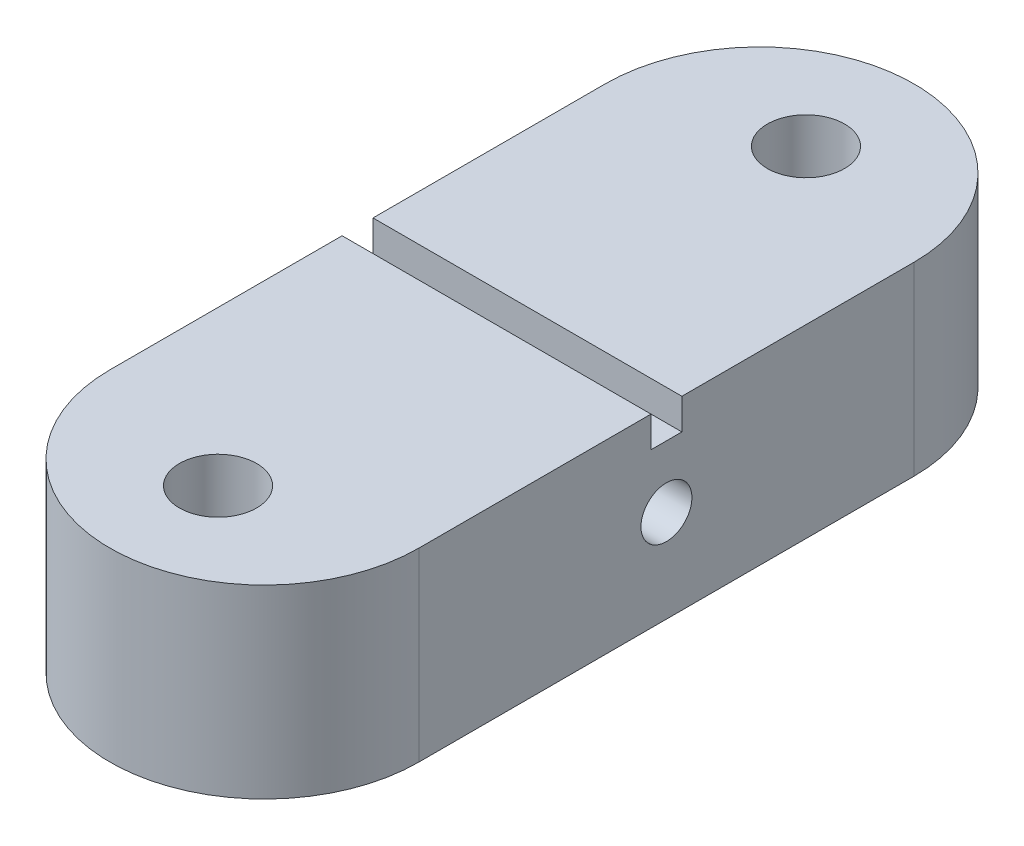
SolidWorks part; units mm, degrees
material "ASTM A36 Steel"
ref_plane "Front Plane" through (0, 0, 0) normal (0, 0, 1) x (1, 0, 0)
ref_plane "Top Plane" through (0, 0, 0) normal (0, 1, 0) x (1, 0, 0)
ref_plane "Right Plane" through (0, 0, 0) normal (1, 0, 0) x (0, 0, -1)
sketch "Sketch1" plane through (0, 0, 0) normal (0, 0, 1) x (1, 0, 0)
  line L1 (10, 6) -> (-10, 6)
  line L2 (10, 6) -> (10, -6)
  line L3 (10, -6) -> (-10, -6)
  line L4 (-10, 6) -> (-10, -6)
  line L5 (0, -6) -> (0, 6) construction
  line L6 (10, 0) -> (-10, 0) construction
  point P0 (0, 0)
  dimension "D1" = 20
  dimension "D2" = 12
extrude "Boss-Extrude1" add sketch "Sketch1" along normal mid plane 52.07
hole_wizard "M6x1.0 Tapped Hole1" positions "Sketch2" profile "Sketch3" tap size "M6x1.0" standard "ANSI Metric" end condition through all
sketch "Sketch2" plane through (0, 6, 0) normal (0, 1, 0) x (1, 0, 0)
  line L0 (0, 19.035) -> (0, -19.035) construction
  line L2 (10, -26.035) -> (-10, -26.035) construction
  point P0 (0, -19.035)
  point P2 (0, 0)
  point P5 (0, 19.035)
  dimension "D1" = 7
sketch "Sketch3" plane through (0, 6, 19.035) normal (1, 0, 0) x (0, 0, 1)
  line L0 (0, 0) -> (0, 12)
  line L1 (0, 12) -> (2.5, 12)
  line L2 (2.5, 12) -> (2.5, 0)
  line L5 (2.5, 0) -> (0, 0)
  line L11 (0, -6.35) -> (0, 107.95) construction
  dimension "Thru Tap Drill Dia." = 5
  dimension "Thru Tap Drill Depth" = 12
cosmetic thread "Hole Thread1" parameters "D2"=6
cosmetic thread "Hole Thread2" parameters "D2"=6
cosmetic thread "Hole Thread3" parameters "D2"=6
sketch "Sketch7" [suppressed] plane through (0, 0, -22.5) normal (0, 0, -1) x (-1, 0, 0)
  line L0 (-10, 7.5) -> (10, 7.5) construction
  line L1 (-1, 5.5) -> (1, 5.5)
  line L2 (-1, 5.5) -> (-1, 7.5)
  line L3 (-1, 7.5) -> (1, 7.5)
  line L4 (1, 5.5) -> (1, 7.5)
  line L5 (0, 7.5) -> (0, 5.5) construction
  line L6 (-1, 6.5) -> (1, 6.5) construction
  line L7 (0, 5.5) -> (0, 0) construction
  point P0 (0, 6.5)
  dimension "D1" = 2
  dimension "D2" = 2
extrude "Cut-Extrude2" [suppressed] cut sketch "Sketch7" against normal through all
other "DeleteFace1" face at (0, -6, 2.5) and patch yes
sketch "Sketch4" plane through (0, 0, 0) normal (1, 0, 0) x (0, 0, -1)
  line L0 (-26.035, 6) -> (26.035, 6) construction
  line L1 (-1, 4) -> (1, 4)
  line L2 (-1, 4) -> (-1, 6)
  line L3 (-1, 6) -> (1, 6)
  line L4 (1, 4) -> (1, 6)
  line L5 (0, 6) -> (0, 4) construction
  line L6 (-1, 5) -> (1, 5) construction
  line L7 (0, 4) -> (0, 0) construction
  point P0 (0, 5)
  dimension "D1" = 2
  dimension "D2" = 2
extrude "Cut-Extrude1" cut sketch "Sketch4" against normal through all both and the other way through all
hole_wizard "M4x0.7 Tapped Hole1" positions "Sketch5" profile "Sketch6" tap size "M4x0.7" standard "ANSI Metric" end condition through all
sketch "Sketch5" plane through (-10, 0, 0) normal (-1, 0, 0) x (0, 0, 1)
  point P0 (0, 0)
sketch "Sketch6" plane through (-10, 0, 0) normal (0, 1, 0) x (0, 0, 1)
  line L0 (0, 0) -> (0, 20)
  line L1 (0, 20) -> (1.65, 20)
  line L2 (1.65, 20) -> (1.65, 0)
  line L5 (1.65, 0) -> (0, 0)
  line L11 (0, -6.35) -> (0, 107.95) construction
  dimension "Thru Tap Drill Dia." = 3.3
  dimension "Thru Tap Drill Depth" = 20
cosmetic thread "Hole Thread4" parameters "D2"=4
fillet "Fillet1" 2 edges at (-10, 0, -26.035) (10, 0, -26.035) type full round first side face at (-10, 0, 1.65) second side face at (10, 0, 1.65) middle face at (0, 0, -26.035)
fillet "Fillet2" 2 edges at (10, 0, 26.035) (-10, 0, 26.035) type full round first side face at (10, 0, 1.65) second side face at (-10, 0, 1.65) middle face at (0, 0, 26.035)
